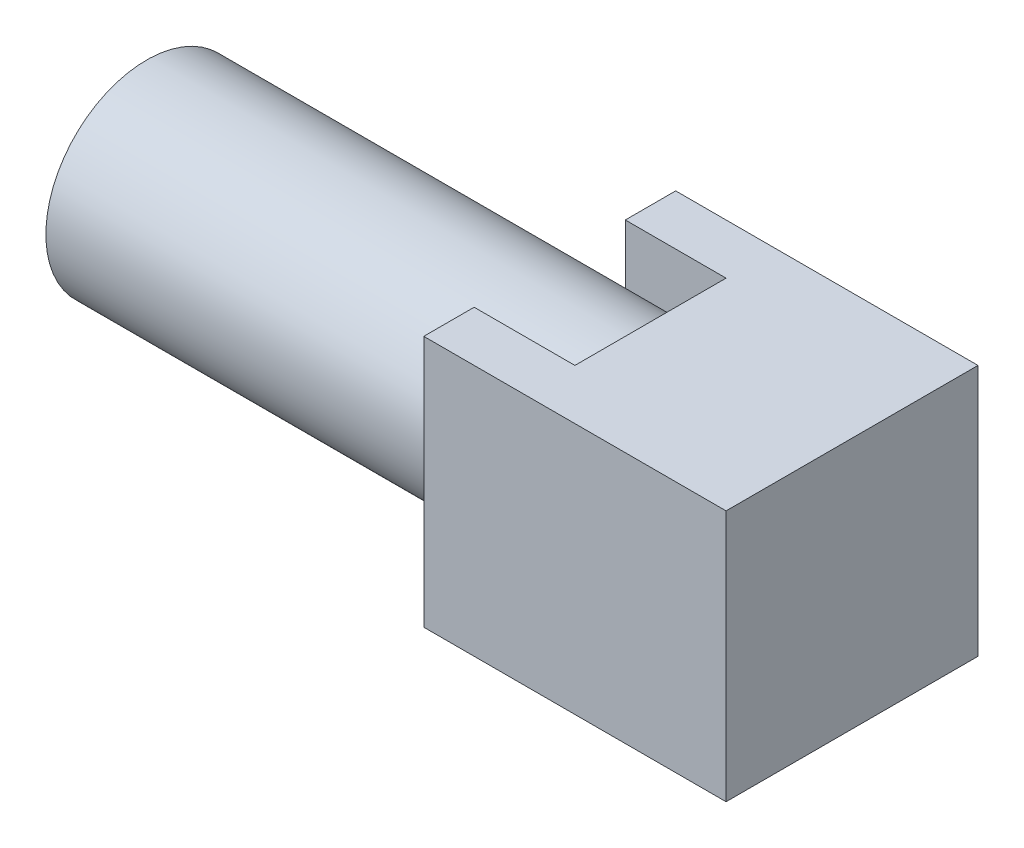
SolidWorks part; units mm, degrees
ref_plane "Front Plane" through (0, 0, 0) normal (0, 0, 1) x (1, 0, 0)
ref_plane "Top Plane" through (0, 0, 0) normal (0, 1, 0) x (1, 0, 0)
ref_plane "Right Plane" through (0, 0, 0) normal (1, 0, 0) x (0, 0, -1)
sketch "Sketch2" plane through (0, 0, 0) normal (1, 0, 0) x (0, 0, -1)
  circle A0 centre (0, 0) radius 12.7
  dimension "D1" = 25.4
extrude "Boss-Extrude1" add sketch "Sketch2" along normal blind 63.5
sketch "Sketch3" plane through (63.5, 0, 0) normal (1, 0, 0) x (0, 0, -1)
  line L1 (-15.875, 15.875) -> (15.875, 15.875)
  line L2 (-15.875, 15.875) -> (-15.875, -15.875)
  line L3 (-15.875, -15.875) -> (15.875, -15.875)
  line L4 (15.875, 15.875) -> (15.875, -15.875)
  line L5 (-15.875, 15.875) -> (15.875, -15.875) construction
  line L6 (-15.875, -15.875) -> (15.875, 15.875) construction
  point P0 (0, 0)
  dimension "D1" = 31.75
  dimension "D2" = 31.75
extrude "Boss-Extrude2" add sketch "Sketch3" along normal blind 25.4
sketch "Sketch6" plane through (0, 0, -15.875) normal (0, 0, -1) x (-1, 0, 0)
  line L1 (-63.5, 15.875) -> (-50.8, 15.875)
  line L2 (-63.5, 15.875) -> (-63.5, -15.875)
  line L3 (-63.5, -15.875) -> (-50.8, -15.875)
  line L4 (-50.8, 15.875) -> (-50.8, -15.875)
  dimension "D1" = 12.7
  dimension "D2" = 31.75
extrude "Boss-Extrude3" add sketch "Sketch6" against normal blind 6.35
mirror "Mirror1" about plane through (0, 0, 0) normal (0, 0, 1) of "Boss-Extrude3"
